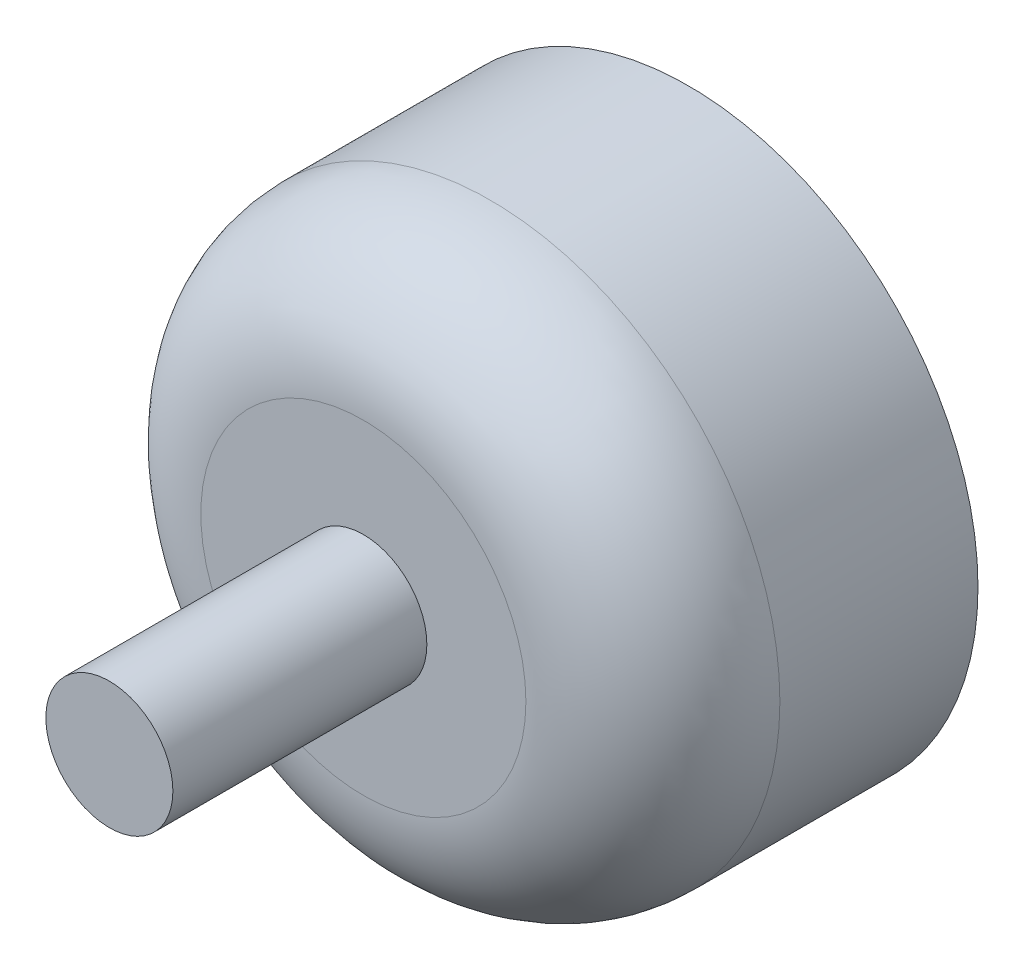
SolidWorks part; units mm, degrees
ref_plane "前视基准面" through (0, 0, 0) normal (0, 0, 1) x (1, 0, 0)
ref_plane "上视基准面" through (0, 0, 0) normal (0, 1, 0) x (1, 0, 0)
ref_plane "右视基准面" through (0, 0, 0) normal (1, 0, 0) x (0, 0, -1)
sketch "草图1" plane through (0, 0, 0) normal (0, 0, 1) x (1, 0, 0)
  circle A0 centre (0, 0) radius 11.4
extrude "凸台-拉伸1" add sketch "草图1" along normal blind 12.8
sketch "草图2" plane through (0, 0, 0) normal (0, 0, -1) x (-1, 0, 0)
  line L0 (0, 0) -> (6, 0) construction
  line L1 (0, 0) -> (0, 6) construction
  circle A0 centre (6, 0) radius 1
  point P0 (0, 0)
extrude "切除-拉伸1" cut sketch "草图2" against normal blind 3
ref_axis "基准轴1" through (0, 0, 13.44) along (0, 0, -1)
pattern_circular "阵列(圆周)1" count 4 every 90 about axis through (0, 0, 13.44) along (0, 0, -1) of "切除-拉伸1"
sketch "草图3" plane through (0, 0, 0) normal (0, 0, -1) x (-1, 0, 0)
  circle A0 centre (0, 0) radius 3
extrude "凸台-拉伸2" add sketch "草图3" along normal blind 0.5
sketch "草图4" plane through (0, 0, -0.5) normal (0, 0, -1) x (-1, 0, 0)
  circle A0 centre (0, 0) radius 1.5
extrude "凸台-拉伸3" add sketch "草图4" along normal blind 1
sketch "草图5" plane through (0, 0, 12.8) normal (0, 0, 1) x (1, 0, 0)
  circle A0 centre (0, 0) radius 2.5
extrude "凸台-拉伸4" add sketch "草图5" along normal blind 10
fillet "圆角1" radius 5 1 edges at (11.4, 0, 12.8)
